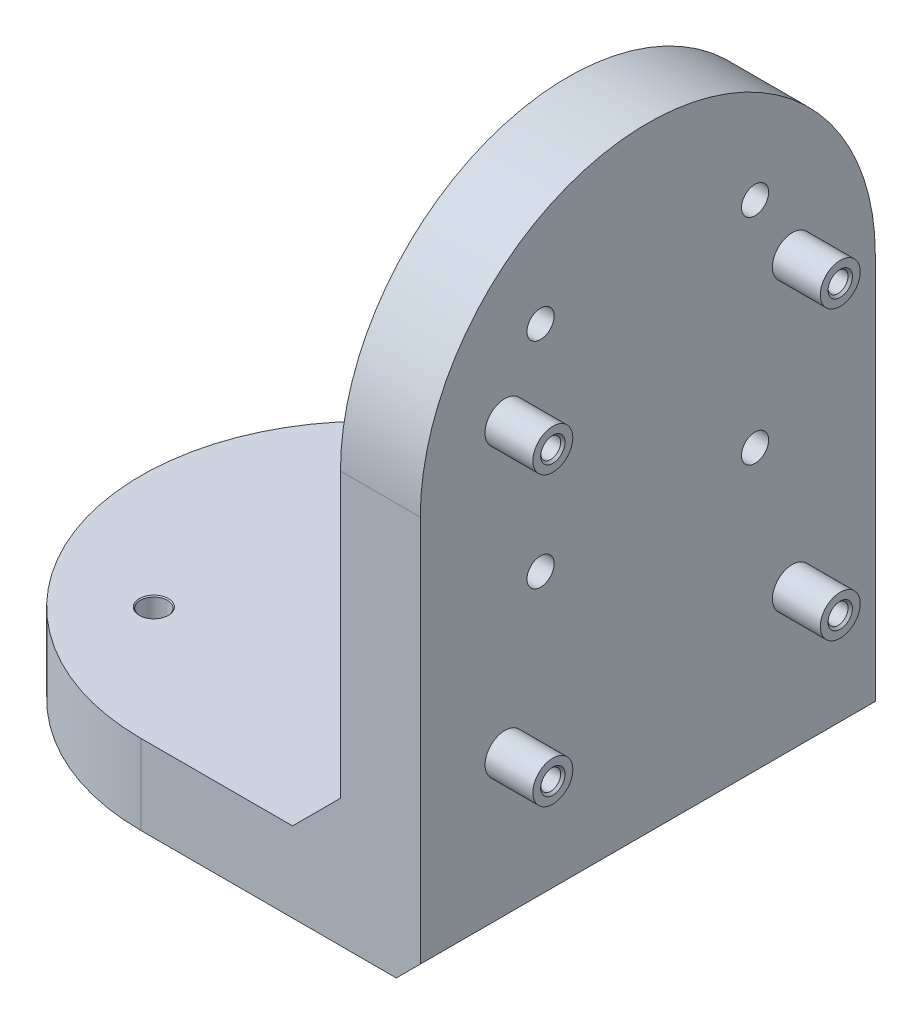
SolidWorks part; units mm, degrees
material "ABS"
ref_plane "前视基准面" through (0, 0, 0) normal (0, 0, 1) x (1, 0, 0)
ref_plane "上视基准面" through (0, 0, 0) normal (0, 1, 0) x (1, 0, 0)
ref_plane "右视基准面" through (0, 0, 0) normal (1, 0, 0) x (0, 0, -1)
other "Configuration Table"
sketch "草图2" plane through (0, 0, 0) normal (0, 1, 0) x (1, 0, 0)
  line L0 (0, 28.5) -> (35, 28.5)
  line L1 (35, 28.5) -> (35, -28.5)
  line L2 (35, -28.5) -> (0, -28.5)
  line L3 (25, 28.5) -> (25, -28.5)
  circle A0 centre (0, 0) radius 28.5 construction
  arc A1 (0, 28.5) -> (0, -28.5) centre (0, 0) ccw
  dimension "D1" = 57
  dimension "D2" = 10
  dimension "D3" = 25
extrude "凸台-拉伸1" add sketch "草图2" along normal blind 10 contours A0 | A0 L2 L3 L0 region at (0.8811, 0, 0)
extrude "凸台-拉伸2" add sketch "草图2<3>" along normal blind 80 contours L0 L3 L2 L1 region at (30, 0, 0)
sketch "草图2<3>" plane through (0, 0, 0) normal (0, 1, 0) x (1, 0, 0) same geometry as "草图2"
sketch "草图6" plane through (0, 10, 0) normal (0, 1, 0) x (1, 0, 0)
  line L0 (0, 0) -> (16.0667, 0) construction
  line L1 (0, 0) -> (20.2453, 20.2453) construction
  circle A0 centre (0, 0) radius 19 construction
  point P8 (13.435, 13.435)
  point P14 (13.435, -13.435)
  point P15 (-13.435, -13.435)
  point P16 (-13.435, 13.435)
  dimension "D1" = 38
  dimension "D2" = 45
  dimension "D3" = 4
hole_wizard "M3 间隙孔2" positions "草图6" profile "草图7" hole size "M3" standard "GB" end condition up to next
sketch "草图7" plane through (-13.435, 10, -13.435) normal (1, 0, 0) x (0, 0, 1)
  line L0 (0, 0) -> (0, 10)
  line L1 (0, 10) -> (1.7, 10)
  line L2 (1.7, 10) -> (1.7, 0.125)
  line L3 (1.7, 0.125) -> (1.825, 0)
  line L5 (1.825, 0) -> (0, 0)
  line L6 (-1.7, 0.125) -> (-1.825, 0) construction
  line L11 (0, -6.35) -> (0, 107.95) construction
  dimension "通孔孔直径" = 3.4
  dimension "通孔孔深度" = 10
  dimension "近端锥形沉头孔直径" = 3.65
  dimension "近端锥形沉头孔角度" = 90
sketch "草图10" plane through (25, 0, 0) normal (-1, 0, 0) x (0, 0, 1)
  line L0 (-28.5, 80) -> (28.5, 80) construction
  line L1 (-28.5, 80) -> (-28.5, 10) construction
  line L2 (28.5, 80) -> (28.5, 10) construction
  line L3 (0, 80) -> (-28.5, 80)
  line L4 (-28.5, 80) -> (-28.5, 51.5)
  line L5 (0, 80) -> (28.5, 80)
  line L6 (28.5, 80) -> (28.5, 51.5)
  circle A0 centre (0, 51.5) radius 28.5
  line M2 (-28.5, 80) -> (-28.5, 10)
  line M4 (28.5, 10) -> (28.5, 80)
  line M5 (28.5, 80) -> (-28.5, 80)
extrude "切除-拉伸1" cut sketch "草图10" against normal up to next contours A0 M5 M2 | A0 M4 M5 region at (25, 73.634, -22.134) region at (25, 73.634, 22.134)
sketch "草图11" plane through (25, 0, 0) normal (-1, 0, 0) x (0, 0, 1)
  line L0 (-28.5, 51.5) -> (28.5, 51.5) construction
  line L1 (0, 51.5) -> (33.5185, 85.0185) construction
  circle A0 centre (0, 51.5) radius 19 construction
  point P9 (13.435, 64.935)
  dimension "D1" = 38
  dimension "D3" = 45
hole_wizard "M3 间隙孔3" positions "草图11" profile "草图12" hole size "M3" standard "GB" end condition up to next
sketch "草图12" plane through (25, 64.935, 13.435) normal (0, 1, 0) x (0, 0, 1)
  line L0 (0, 0) -> (0, 10)
  line L1 (0, 10) -> (1.7, 10)
  line L2 (1.7, 10) -> (1.7, 0.125)
  line L3 (1.7, 0.125) -> (1.825, 0)
  line L5 (1.825, 0) -> (0, 0)
  line L6 (-1.7, 0.125) -> (-1.825, 0) construction
  line L11 (0, -6.35) -> (0, 107.95) construction
  dimension "通孔孔直径" = 3.4
  dimension "通孔孔深度" = 10
  dimension "近端锥形沉头孔直径" = 3.65
  dimension "近端锥形沉头孔角度" = 90
chamfer "倒角2" distance 3 angle 45 1 edges at (35, 0, 0)
chamfer "倒角3" distance 6 angle 45 1 edges at (25, 10, 0)
ref_axis "基准轴1" through (35, 51.5, 0) along (-1, 0, 0)
pattern_circular "阵列(圆周)1" count 4 over 360 about axis through (35, 51.5, 0) along (-1, 0, 0) of "M3 间隙孔3"
sketch "草图13" plane through (35, 0, 0) normal (1, 0, 0) x (0, 0, -1)
  line L0 (-17.8917, 56.5571) -> (18.1083, 56.5571) construction
  line L1 (-17.8917, 56.5571) -> (-17.8917, 20.5571) construction
  circle A0 centre (-17.8917, 56.5571) radius 2.5
  circle A1 centre (18.1083, 56.5571) radius 2.5
  circle A2 centre (18.1083, 20.5571) radius 2.5
  circle A3 centre (-17.8917, 20.5571) radius 2.5
  point P0 (-17.8917, 56.5571)
  dimension "D5" = 5
  dimension "D3" = 36
  dimension "D4" = 36
  dimension "D1" = 2
  dimension "D2" = 2
extrude "凸台-拉伸3" add sketch "草图13" along normal blind 6
sketch "草图16" plane through (41, 0, 0) normal (1, 0, 0) x (0, 0, -1)
  point P0 (-17.8917, 56.5571)
  point P3 (18.1083, 56.5571)
  point P6 (-17.8917, 20.5571)
  point P9 (18.1083, 20.5571)
hole_wizard "M3 螺纹孔1" positions "草图16" profile "草图15" tap size "M3" standard "GB"
sketch "草图15" plane through (41, 56.5571, 17.8917) normal (0, 1, 0) x (0, 0, -1)
  line L0 (0, 0) -> (0, 5.7511)
  line L1 (0, 5.7511) -> (1.25, 5)
  line L2 (1.25, 5) -> (1.25, 0.275)
  line L3 (1.25, 0.275) -> (1.525, 0)
  line L5 (1.525, 0) -> (0, 0)
  line L6 (-1.25, 0.275) -> (-1.525, 0) construction
  line L10 (0, 5.7511) -> (-1.25, 5) construction
  line L11 (0, -6.35) -> (0, 107.95) construction
  dimension "螺纹孔钻头直径" = 2.5
  dimension "螺纹孔钻头深度" = 5
  dimension "近端锥形沉头孔直径" = 3.05
  dimension "近端锥形沉头孔角度" = 90
  dimension "导头角度" = 118
cosmetic thread "孔螺纹线1" parameters "D1"=3.5, "D2"=3
cosmetic thread "孔螺纹线2" parameters "D1"=3.5, "D2"=3
cosmetic thread "孔螺纹线3" parameters "D1"=3.5, "D2"=3
cosmetic thread "孔螺纹线4" parameters "D1"=3.5, "D2"=3
